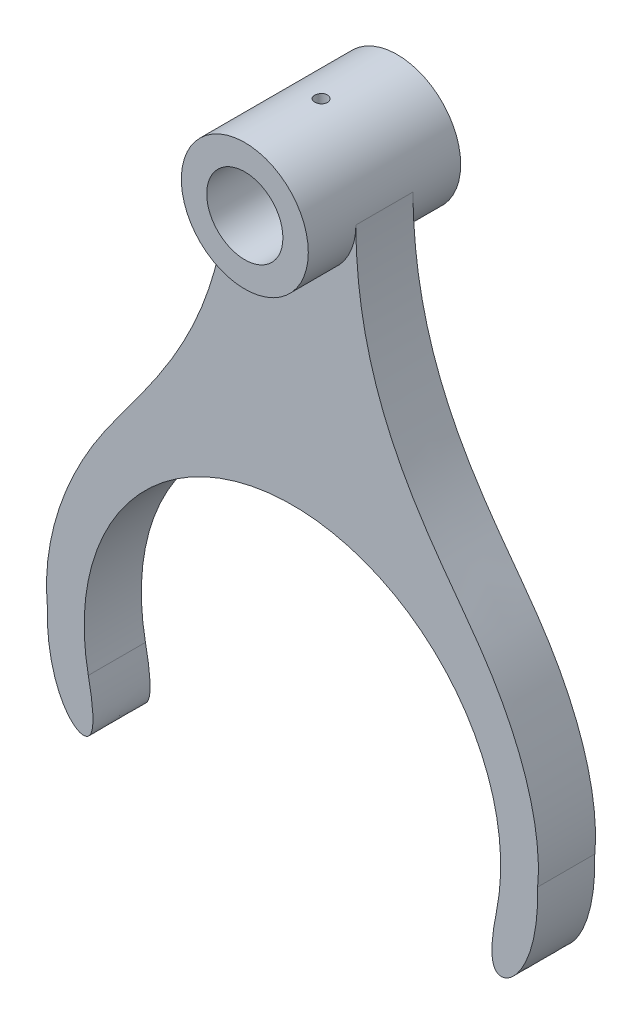
SolidWorks part; units mm, degrees
ref_plane "Front Plane" through (0, 0, 0) normal (0, 0, 1) x (1, 0, 0)
ref_plane "Top Plane" through (0, 0, 0) normal (0, 1, 0) x (1, 0, 0)
ref_plane "Right Plane" through (0, 0, 0) normal (1, 0, 0) x (0, 0, -1)
other "Default"
sketch "Sketch1" plane through (0, 0, 0) normal (0, 0, 1) x (1, 0, 0)
  line L1 (0, 0) -> (0, 200.3122) construction
  arc A0 (80.3693, -16.2717) -> (-80.3693, -16.2717) centre (0, 0) ccw
  circle A2 centre (0, 190) radius 25
  circle A3 centre (0, 190) radius 15
  spline S0 degree 3 poles (-96.5397, 0) (-96.4933, 1.7302) (-104.3462, 48.7695) (-25, 126.8484) (-25, 190) knots 0 0 0 0 0.598566 1 1 1 1
  spline S1 degree 3 poles (96.5397, 0) (96.4933, 1.7302) (104.3462, 48.7695) (25, 126.8484) (25, 190) knots 0 0 0 0 0.598566 1 1 1 1
  spline S2 degree 3 poles (-96.5397, 0) (-97.3266, -29.3315) (-77.4735, -47.5739) (-78.1125, -27.4188) (-80.3693, -16.2717) knots 0 0 0 0 0.663724 1 1 1 1
  spline S3 degree 3 poles (96.5397, 0) (97.3266, -29.3315) (77.4735, -47.5739) (78.1125, -27.4188) (80.3693, -16.2717) knots 0 0 0 0 0.663724 1 1 1 1
  dimension "D1" = 164
  dimension "D2" = 50
  dimension "D3" = 30
  dimension "D4" = 190
extrude "Boss-Extrude1" add sketch "Sketch1" along normal mid plane 22.5 contours A0 L1 A2 S0 S2 | L1 A0 S3 S1 A2 region at (-42.5577, 86.0625, 0) region at (42.5571, 86.0601, 0)
extrude "Boss-Extrude2" add sketch "Sketch1<3>" along normal mid plane 60 contours A2 L1 A3 region at (-17.1777, 172.8223, 0)
sketch "Sketch1<3>" plane through (0, 0, 0) normal (0, 0, 1) x (1, 0, 0) same geometry as "Sketch1"
ref_plane "Plane1" through (0, 180, 0) normal (0, 1, 0) x (1, 0, 0)
sketch "Sketch3" plane through (0, 180, 0) normal (0, 1, 0) x (1, 0, 0)
  circle A0 centre (0, 0) radius 2.5
  dimension "D1" = 5
extrude "Cut-Extrude1" cut sketch "Sketch3" along normal through all
